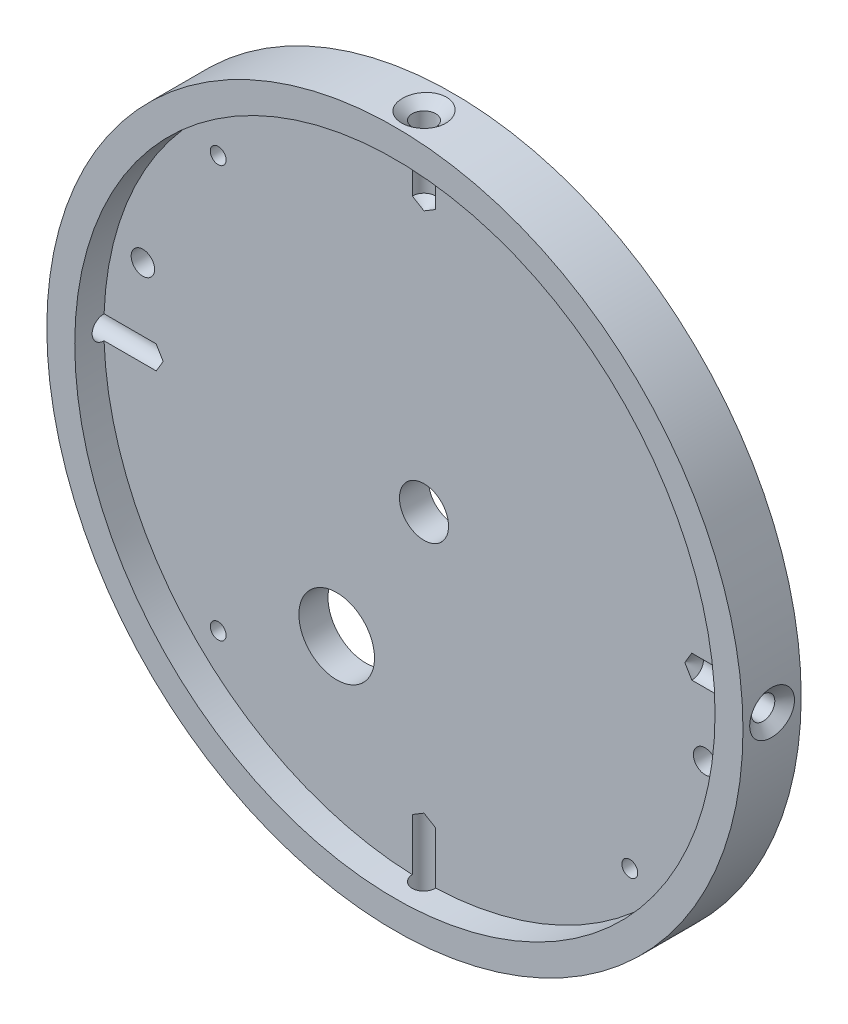
SolidWorks part; units mm, degrees
material "6061 Alloy"
ref_plane "Front Plane" through (0, 0, 0) normal (0, 0, 1) x (1, 0, 0)
ref_plane "Top Plane" through (0, 0, 0) normal (0, 1, 0) x (1, 0, 0)
ref_plane "Right Plane" through (0, 0, 0) normal (1, 0, 0) x (0, 0, -1)
sketch "Bulkhead Body Profile" plane through (0, 0, 0) normal (0, 0, 1) x (1, 0, 0)
  circle A0 centre (0, 0) radius 75.946
  dimension "D1" = 151.892
extrude "Bulkhead Body" add sketch "Bulkhead Body Profile" along normal blind 12.7
sketch "Bulkhead Inside Profile" plane through (0, 0, 12.7) normal (0, 0, 1) x (1, 0, 0)
  circle A0 centre (0, 0) radius 69.85
  dimension "D1" = 139.7
extrude "Bulkhead Inside Cut" cut sketch "Bulkhead Inside Profile" against normal blind 6.35
sketch "Bulkhead Inside Hole Profile" plane through (0, 0, 6.35) normal (0, 0, 1) x (1, 0, 0)
  line L0 (-19.05, -32.9956) -> (0, 0) construction
  line L1 (0, 0) -> (0, -69.85) construction
  line L2 (-61.3363, 16.435) -> (61.3363, -16.435) construction
  line L3 (0, 0) -> (-69.85, 0) construction
  line L4 (-44.9013, 44.9013) -> (44.9013, -44.9013) construction
  line L5 (-44.9013, -44.9013) -> (44.9013, 44.9013) construction
  circle A0 centre (0, 0) radius 5.3581
  circle A1 centre (-19.05, -32.9956) radius 8.25
  circle A2 centre (-61.3363, 16.435) radius 2.5527
  circle A3 centre (61.3363, -16.435) radius 2.5527
  circle A4 centre (44.9013, 44.9013) radius 1.7272
  circle A5 centre (-44.9013, 44.9013) radius 1.7272
  circle A6 centre (-44.9013, -44.9013) radius 1.7272
  circle A7 centre (44.9013, -44.9013) radius 1.7272
  circle A8 centre (0, 0) radius 69.85 construction
  circle A9 centre (0, 0) radius 69.85 construction
  dimension "D1" = 10.7163
  dimension "D2" = 16.5
  dimension "D3" = 5.1054
  dimension "D4" = 38.1
  dimension "D5" = 3.4544
  dimension "D6" = 30
  dimension "D8" = 63.5
  dimension "D7" = 15
  dimension "D9" = 63.5
  dimension "D10" = 45
extrude "Bulkhead Inside Holes" cut sketch "Bulkhead Inside Hole Profile" against normal through all
ref_plane "Plane1" through (0, 75.946, 0) normal (0, 1, 0) x (1, 0, 0)
sketch "Sketch4" plane through (0, 75.946, 0) normal (0, 1, 0) x (1, 0, 0)
  line L0 (-75.946, 0) -> (75.946, -12.7) construction
  line L1 (-75.946, -12.7) -> (75.946, -12.7) construction
  line L2 (-75.946, -12.7) -> (-75.946, 0) construction
  line L3 (-75.946, 0) -> (75.946, 0) construction
  line L4 (75.946, -12.7) -> (75.946, 0) construction
  line L5 (75.946, 0) -> (-75.946, -12.7) construction
  point P0 (0, -6.35)
hole_wizard "Shear Pin Cut" positions "Sketch4" profile "Sketch5" countersink size "#10" standard "ANSI Inch"
sketch "Sketch5" plane through (0, 75.946, 6.35) normal (1, 0, 0) x (0, 0, 1)
  line L0 (0, 0) -> (0, 19.05)
  line L1 (0, 19.05) -> (2.5527, 17.5162)
  line L2 (2.5527, 17.5162) -> (2.5527, 1.9608)
  line L3 (2.5527, 1.9608) -> (4.8895, 0)
  line L5 (4.8895, 0) -> (0, 0)
  line L6 (-2.5527, 1.9608) -> (-4.8895, 0) construction
  line L10 (0, 19.05) -> (-2.5527, 17.5162) construction
  line L11 (0, -6.35) -> (0, 107.95) construction
  dimension "Hole Dia." = 5.1054
  dimension "Hole Depth" = 19.05
  dimension "Near C'Sink Dia." = 9.779
  dimension "Near C'Sink Angle" = 100
  dimension "Drill Angle" = 118
pattern_circular "Shear Pin Pattern" count 4 over 360 about axis through (0, 0, 12.7) along (0, 0, 1) of "Shear Pin Cut"
